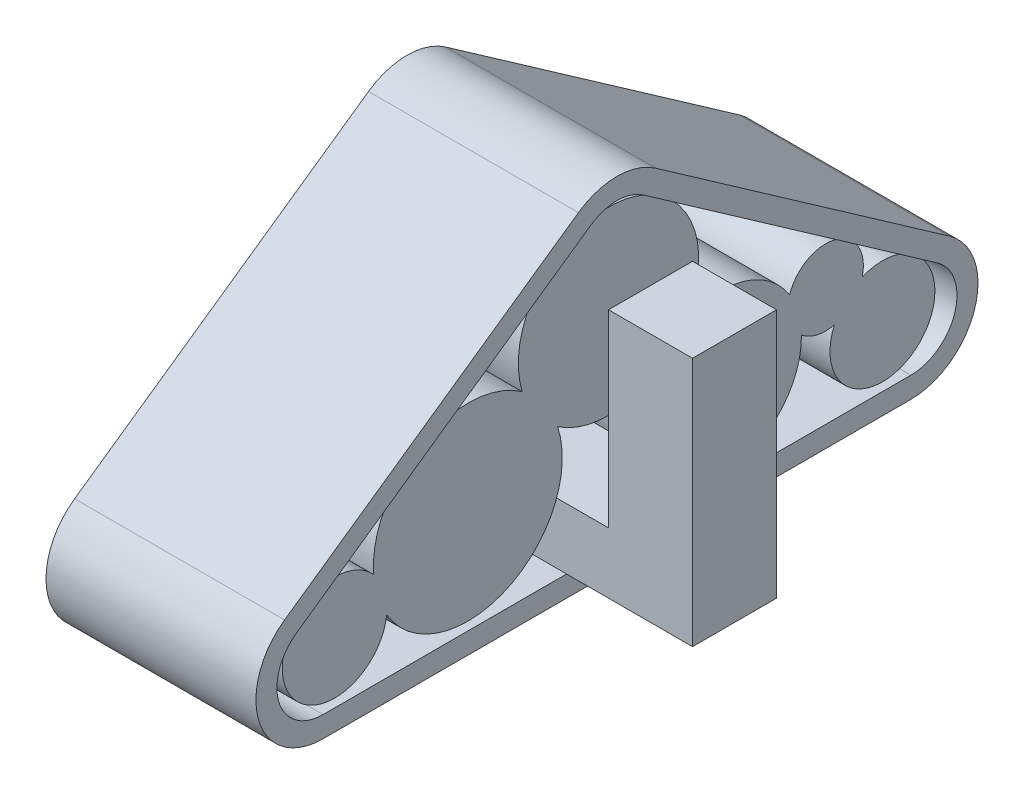
SolidWorks part; units mm, degrees
ref_plane "Front" through (0, 0, 0) normal (0, 0, 1) x (1, 0, 0)
ref_plane "Top" through (0, 0, 0) normal (0, 1, 0) x (1, 0, 0)
ref_plane "Right" through (0, 0, 0) normal (1, 0, 0) x (0, 0, -1)
sketch "Sketch1" plane through (0, 0, 0) normal (1, 0, 0) x (0, 0, -1)
  line L0 (3, 0) -> (-3, 0)
  line L1 (6.641, 0) -> (-6.641, 0) construction
  line L2 (-3, 0) -> (-3.5, 0)
  line L3 (-3.9589, 1.4553) -> (-0.4589, 3.906)
  line L4 (0, 2.325) -> (0, -2.325) construction
  line L5 (3.9589, 1.4553) -> (0.4589, 3.906)
  line L6 (3, 0) -> (3.5, 0)
  line L8 (0.3155, 3.7013) -> (3.8155, 1.2505)
  line L9 (3.5, 0.25) -> (-3.5, 0.25)
  line L10 (-0.3155, 3.7013) -> (-3.8155, 1.2505)
  line L11 (0, 3.8797) -> (0, 3.2507)
  arc A0 (3.9589, 1.4553) -> (3.5, 0) centre (3.5, 0.8) cw
  arc A1 (-3.5, 0) -> (-3.9589, 1.4553) centre (-3.5, 0.8) cw
  arc A2 (-0.4589, 3.906) -> (0.4589, 3.906) centre (0, 3.2507) cw
  arc A3 (-3.8155, 1.2505) -> (-3.5, 0.25) centre (-3.5, 0.8) ccw
  arc A5 (3.8155, 1.2505) -> (3.5, 0.25) centre (3.5, 0.8) cw
  arc A6 (0.3155, 3.7013) -> (-0.3155, 3.7013) centre (0, 3.2507) ccw
  point P11 (0, 0)
  point P13 (6.0373, 0)
  point P16 (-6.0373, 0)
  point P19 (0, 4.2273)
  dimension "D2" = 0.8
  dimension "D4" = 0.8
  dimension "D5" = 1.1
  dimension "D6" = 1.1
  dimension "D1" = 7
  dimension "D3" = 35
  dimension "D7" = 0.25
extrude "Treads" add sketch "Sketch1" along normal blind 2.5 contours L8 A6 L10 A3 L9 A5 | L10 A3 L9 A5 L8 A6 | L3 A2 L5 A0 L6 L0 L2 A1 region at (0, 1.5312, 0)
ref_plane "Plane1" through (1.25, 0, 0) normal (1, 0, 0) x (0, 0, -1)
sketch "Sketch3" plane through (1.25, 0, 0) normal (1, 0, 0) x (0, 0, -1)
  line L0 (-0.3155, 3.7013) -> (-3.8155, 1.2505) construction
  line L1 (3.5, 0.25) -> (-3.5, 0.25) construction
  line L2 (0, 1.375) -> (0, -1.375) construction
  line L7 (-0.6, 0.25) -> (0.4, 0.25)
  line L8 (-0.6, 0.25) -> (-0.6, 0.975)
  line L9 (0.4, 0.25) -> (0.4, 0.975)
  line L10 (0.4, 0.975) -> (-0.6, 0.975)
  line L11 (0.3155, 3.7013) -> (3.8155, 1.2505) construction
  circle A0 centre (-3.2621, 0.875) radius 0.625
  circle A1 centre (3.2621, 0.875) radius 0.625
  circle A2 centre (-1.6763, 1.375) radius 1.125
  circle A3 centre (0, 2.6098) radius 1.075
  circle A4 centre (1.3472, 1.2) radius 0.95
  circle A5 centre (2.5852, 1.5627) radius 0.45
  point P6 (0, 0.5)
  point P23 (2.3809, 1.4998)
  point P24 (0, 0)
  point P25 (0, 0)
  point P26 (2.4862, 1.375)
  point P27 (0, 0)
  point P28 (0, 0)
  point P29 (2.4628, 1.4413)
  dimension "D1" = 1.25
  dimension "D2" = 0.625
  dimension "D3" = 0.625
  dimension "D6" = 2.25
  dimension "D7" = 1.125
  dimension "D8" = 1.125
  dimension "D9" = 2.15
  dimension "D10" = 1.075
  dimension "D11" = 1.9
  dimension "D12" = 0.95
  dimension "D13" = 1.95
  dimension "D15" = 0.9
  dimension "D16" = 0.45
  dimension "D4" = 1
  dimension "D5" = 0.725
  dimension "D14" = 0.6
  dimension "D17" = 1.29
extrude "Circles" add sketch "Sketch3" along normal blind 1.15 and the other way blind 1.15 separate body contours A2 A0 | A3 A2 A0 | A4 A3 A2 | A5 A4 A3 | A4 A5 A1 | A4 A5 | A5 A1 | A1 A5 | A0 | A2 | A3 region at (1.25, 1.3684, 1.6806) region at (1.25, 0.8706, 3.2762) region at (1.25, 2.6251, -0.0074) region at (1.25, 1.1901, -1.3418) region at (1.25, 1.5871, -2.593) region at (1.25, 1.4527, -2.2099) region at (1.25, 0.8632, -3.2738) region at (1.25, 1.2825, -2.861)
extrude "Bottom of Connector" add sketch "Sketch3<5>" along normal blind 2.75 and the other way blind 1.25 contours L9 L10 L8 L7 region at (1.25, 0.6125, 0.1)
sketch "Sketch3<5>" plane through (1.25, 0, 0) normal (1, 0, 0) x (0, 0, -1) same geometry as "Sketch3"
sketch "Sketch4" plane through (0, 0.975, 0) normal (0, 1, 0) x (1, 0, 0)
  line L0 (0, -0.6) -> (4, -0.6) construction
  line L1 (4, 0.4) -> (3, 0.4)
  line L2 (4, 0.4) -> (4, -0.6)
  line L3 (4, -0.6) -> (3, -0.6)
  line L4 (3, 0.4) -> (3, -0.6)
  dimension "D1" = 1
extrude "Top of Connector" add sketch "Sketch4" along normal blind 2.25
